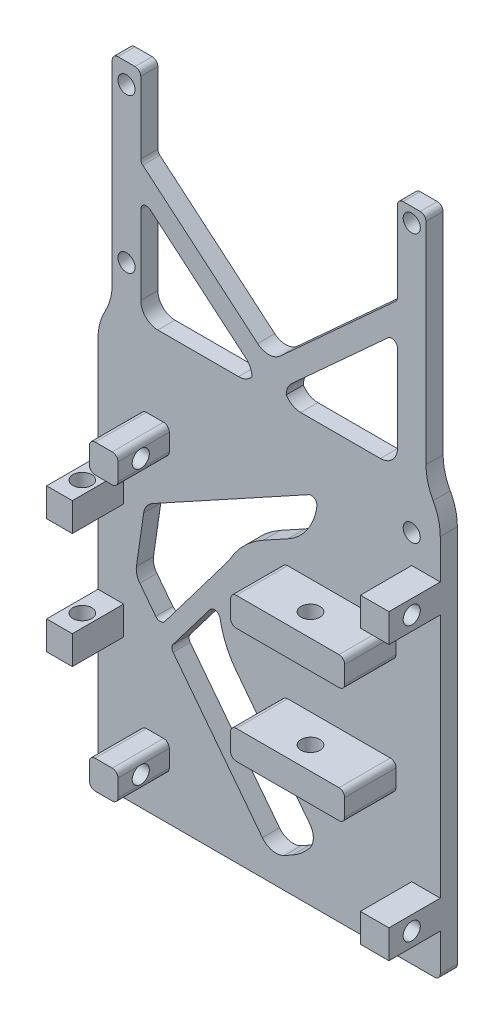
SolidWorks part; units mm, degrees
ref_plane "Front Plane" through (0, 0, 0) normal (0, 0, 1) x (1, 0, 0)
ref_plane "Top Plane" through (0, 0, 0) normal (0, 1, 0) x (1, 0, 0)
ref_plane "Right Plane" through (0, 0, 0) normal (1, 0, 0) x (0, 0, -1)
sketch "Sketch1" plane through (0, 0, 0) normal (0, 0, 1) x (1, 0, 0)
  line L1 (-63.7571, 35.9548) -> (-3.7571, 35.9548)
  line L2 (-63.7571, 35.9548) -> (-63.7571, -38.0452)
  line L3 (-63.7571, -38.0452) -> (-3.7571, -38.0452)
  line L4 (-3.7571, 35.9548) -> (-3.7571, -38.0452)
  dimension "D1" = 74
  dimension "D2" = 60
extrude "Boss-Extrude1" add sketch "Sketch1" along normal blind 3
sketch "Sketch2" plane through (0, 0, 3) normal (0, 0, 1) x (1, 0, 0)
  line L0 (-59.2571, -1.0452) -> (-63.7571, -1.0452) construction
  line L1 (-63.7571, 6.5548) -> (-59.2571, 6.5548) construction
  line L2 (-63.7571, 6.5548) -> (-63.7571, -8.6452) construction
  line L3 (-63.7571, -8.6452) -> (-59.2571, -8.6452) construction
  line L4 (-59.2571, 6.5548) -> (-59.2571, -8.6452) construction
  line L5 (-63.7571, 35.9548) -> (-63.7571, -38.0452) construction
  line L6 (-63.7571, -1.0452) -> (-3.7571, -1.0452) construction
  line L7 (-63.7571, 6.5548) -> (-59.2571, 6.5548)
  line L8 (-63.7571, 6.5548) -> (-63.7571, 11.5548)
  line L9 (-63.7571, 11.5548) -> (-59.2571, 11.5548)
  line L10 (-59.2571, 6.5548) -> (-59.2571, 11.5548)
  line L11 (-63.7571, -8.6452) -> (-59.2571, -8.6452)
  line L12 (-63.7571, -8.6452) -> (-63.7571, -13.6452)
  line L13 (-63.7571, -13.6452) -> (-59.2571, -13.6452)
  line L14 (-59.2571, -8.6452) -> (-59.2571, -13.6452)
  line L15 (-31.5071, -8.6452) -> (-11.5071, -8.6452)
  line L16 (-31.5071, -8.6452) -> (-31.5071, -13.6452)
  line L17 (-31.5071, -13.6452) -> (-11.5071, -13.6452)
  line L18 (-11.5071, -8.6452) -> (-11.5071, -13.6452)
  line L19 (-31.5071, -8.6452) -> (-11.5071, -13.6452) construction
  line L20 (-31.5071, -13.6452) -> (-11.5071, -8.6452) construction
  line L21 (-31.5071, 11.5548) -> (-11.5071, 11.5548)
  line L22 (-31.5071, 11.5548) -> (-31.5071, 6.5548)
  line L23 (-31.5071, 6.5548) -> (-11.5071, 6.5548)
  line L24 (-11.5071, 11.5548) -> (-11.5071, 6.5548)
  line L25 (-31.5071, 11.5548) -> (-11.5071, 6.5548) construction
  line L26 (-31.5071, 6.5548) -> (-11.5071, 11.5548) construction
  line L29 (-63.7571, -38.0452) -> (-3.7571, -38.0452) construction
  line L30 (-3.7571, -38.0452) -> (-3.7571, 35.9548) construction
  line L31 (-56.2571, -25.5452) -> (-51.2571, -25.5452)
  line L32 (-56.2571, -25.5452) -> (-56.2571, -30.5452)
  line L33 (-56.2571, -30.5452) -> (-51.2571, -30.5452)
  line L34 (-51.2571, -25.5452) -> (-51.2571, -30.5452)
  line L35 (-56.2571, -25.5452) -> (-51.2571, -30.5452) construction
  line L36 (-56.2571, -30.5452) -> (-51.2571, -25.5452) construction
  line L37 (-56.2571, 22.4548) -> (-51.2571, 22.4548)
  line L38 (-56.2571, 22.4548) -> (-56.2571, 17.4548)
  line L39 (-56.2571, 17.4548) -> (-51.2571, 17.4548)
  line L40 (-51.2571, 22.4548) -> (-51.2571, 17.4548)
  line L41 (-56.2571, 22.4548) -> (-51.2571, 17.4548) construction
  line L42 (-56.2571, 17.4548) -> (-51.2571, 22.4548) construction
  line L43 (-3.7571, -25.5452) -> (-8.7571, -25.5452)
  line L44 (-3.7571, -25.5452) -> (-3.7571, -30.5452)
  line L45 (-3.7571, -30.5452) -> (-8.7571, -30.5452)
  line L46 (-8.7571, -25.5452) -> (-8.7571, -30.5452)
  line L48 (-3.7571, 22.4548) -> (-8.7571, 22.4548)
  line L49 (-3.7571, 22.4548) -> (-3.7571, 17.4548)
  line L50 (-3.7571, 17.4548) -> (-8.7571, 17.4548)
  line L51 (-8.7571, 22.4548) -> (-8.7571, 17.4548)
  circle A0 centre (-61.5071, 9.0548) radius 1.5 construction
  circle A1 centre (-61.5071, -11.1452) radius 1.5 construction
  circle A2 centre (-21.5071, -11.1452) radius 1.3356 construction
  circle A3 centre (-21.5071, 9.0548) radius 1.3456 construction
  circle A4 centre (-53.7571, -28.0452) radius 1.5 construction
  circle A5 centre (-53.7571, 19.9548) radius 1.3233 construction
  point P8 (-63.7571, -1.0452)
  dimension "D7" = 3
  dimension "D8" = 3
  dimension "D9" = 40
  dimension "D10" = 40
  dimension "D12" = 2.25
  dimension "D13" = 2.5
  dimension "D14" = 2.5
  dimension "D15" = 2.25
  dimension "D19" = 10
  dimension "D20" = 10
  dimension "D21" = 3
  dimension "D24" = 48
  dimension "D1" = 15.2
  dimension "D2" = 4.5
  dimension "D3" = 0
  dimension "D4" = 0
  dimension "D5" = 5
  dimension "D6" = 5
  dimension "D11" = 7.6
  dimension "D16" = 20
  dimension "D17" = 20
  dimension "D18" = 7.6
  dimension "D22" = 5
  dimension "D23" = 5
  dimension "D25" = 5
  dimension "D26" = 5
  dimension "D27" = 5
  dimension "D28" = 5
extrude "Boss-Extrude2" add sketch "Sketch2" along normal blind 9
sketch "Sketch3" plane through (0, -13.6452, 0) normal (0, -1, 0) x (1, 0, 0)
  line L0 (-31.5071, 3) -> (-11.5071, 3) construction
  line L1 (-63.7571, 3) -> (-59.2571, 3) construction
  circle A0 centre (-21.5071, 8) radius 1.6536
  circle A1 centre (-61.5071, 8) radius 1.6536
  point P4 (-21.5071, 3)
  point P7 (-61.5071, 3)
  dimension "D1" = 5
  dimension "D2" = 5
extrude "Cut-Extrude1" cut sketch "Sketch3" against normal blind 26
sketch "Sketch4" plane through (-56.2571, 0, 0) normal (-1, 0, 0) x (0, 0, 1)
  line L0 (3, -25.5452) -> (3, -30.5452) construction
  line L1 (3, 22.4548) -> (3, 17.4548) construction
  circle A0 centre (8, 19.9548) radius 1.5
  circle A1 centre (8, -28.0452) radius 1.5
  dimension "D1" = 3
  dimension "D2" = 3
  dimension "D3" = 5
  dimension "D4" = 5
extrude "Cut-Extrude2" cut sketch "Sketch4" against normal blind 59
sketch "Sketch5" plane through (0, 0, 3) normal (0, 0, 1) x (1, 0, 0)
  line L0 (-58.7571, 27.4548) -> (-8.7571, 27.4548) construction
  line L1 (-63.7571, 35.9548) -> (-63.7571, 11.5548) construction
  line L2 (-3.7571, 22.4548) -> (-8.7571, 22.4548) construction
  line L3 (-3.7571, 35.9548) -> (-63.7571, 35.9548) construction
  line L4 (-3.7571, 22.4548) -> (-3.7571, 35.9548) construction
  line L6 (-61.2571, 35.9548) -> (-56.2571, 35.9548)
  line L7 (-61.2571, 35.9548) -> (-61.2571, 73.9548)
  line L8 (-61.2571, 73.9548) -> (-56.2571, 73.9548)
  line L9 (-56.2571, 35.9548) -> (-56.2571, 73.9548)
  line L10 (-6.2571, 35.9548) -> (-11.2571, 35.9548)
  line L11 (-6.2571, 35.9548) -> (-6.2571, 76.9548)
  line L12 (-6.2571, 76.9548) -> (-11.2571, 76.9548)
  line L13 (-11.2571, 35.9548) -> (-11.2571, 76.9548)
  circle A0 centre (-58.7571, 27.4548) radius 1.3883 construction
  circle A1 centre (-8.7571, 27.4548) radius 1.4141
  circle A2 centre (-8.7571, 74.4548) radius 1.5
  circle A3 centre (-58.7571, 70.4548) radius 1.5
  circle A4 centre (-58.7571, 43.4548) radius 1.5
  dimension "D2" = 5
  dimension "D3" = 5
  dimension "D4" = 47
  dimension "D5" = 3
  dimension "D6" = 4
  dimension "D7" = 3
  dimension "D8" = 27
  dimension "D9" = 3
  dimension "D10" = 38.5
  dimension "D11" = 5
  dimension "D12" = 34.5
  dimension "D1" = 50
  dimension "D13" = 38
  dimension "D14" = 5
  dimension "D15" = 5
  dimension "D16" = 2.5
  dimension "D17" = 2.5
  dimension "D18" = 41
extrude "Boss-Extrude3" add sketch "Sketch5" against normal blind 3
sketch "Sketch6" plane through (0, 0, 3) normal (0, 0, 1) x (1, 0, 0)
  circle A0 centre (-8.7571, 27.4548) radius 1.5
  circle A1 centre (-8.7571, 74.4548) radius 1.5 construction
  dimension "D1" = 3
  dimension "D2" = 47
extrude "Cut-Extrude3" cut sketch "Sketch6" against normal blind 3
sketch "Sketch7" plane through (0, 0, 3) normal (0, 0, 1) x (1, 0, 0)
  line L0 (-56.2571, 54.9548) -> (-36.7571, 38.4881)
  line L1 (-56.2571, 35.9548) -> (-56.2571, 73.9548) construction
  line L2 (-11.2571, 35.9548) -> (-56.2571, 35.9548) construction
  line L3 (-30.7571, 38.6881) -> (-30.7571, 35.9548)
  line L4 (-33.7571, 40.9548) -> (-56.2571, 59.9548)
  line L5 (-56.2571, 59.9548) -> (-56.2571, 54.9548)
  line L6 (-30.7571, 38.6881) -> (-11.2571, 56.4548)
  line L7 (-11.2571, 76.9548) -> (-11.2571, 35.9548) construction
  line L8 (-33.7571, 40.9548) -> (-11.2571, 61.4548)
  line L9 (-11.2571, 61.4548) -> (-11.2571, 56.4548)
  line L10 (-36.7571, 38.4881) -> (-36.7571, 35.9548)
  line L11 (-36.7571, 35.9548) -> (-30.7571, 35.9548)
  dimension "D2" = 5
  dimension "D3" = 5
extrude "Boss-Extrude4" add sketch "Sketch7" against normal blind 3
fillet "Fillet1" radius 10 1 edges at (-3.7571, 35.9548, 1.5)
fillet "Fillet2" radius 10 1 edges at (-63.7571, 35.9548, 1.5)
fillet "Fillet3" radius 10 1 edges at (-6.2571, 35.9548, 1.5)
fillet "Fillet4" radius 10 1 edges
fillet "Fillet5" radius 3 1 edges at (-33.7571, 40.9548, 1.5)
fillet "Fillet6" radius 3 1 edges at (-30.7571, 38.6881, 1.5)
fillet "Fillet7" radius 3 1 edges at (-30.7571, 35.9548, 1.5)
fillet "Fillet8" radius 3 1 edges at (-36.7571, 38.4881, 1.5)
fillet "Fillet9" radius 3 1 edges at (-36.7571, 35.9548, 1.5)
fillet "Fillet10" radius 3 1 edges at (-11.2571, 35.9548, 1.5)
fillet "Fillet11" radius 3 1 edges
fillet "Fillet12" radius 1 1 edges at (-56.2571, 54.9548, 1.5)
fillet "Fillet13" radius 1 1 edges at (-11.2571, 56.4548, 1.5)
fillet "Fillet14" radius 1 1 edges at (-11.2571, 61.4548, 1.5)
fillet "Fillet15" radius 1 1 edges at (-56.2571, 59.9548, 1.5)
sketch "Sketch8" plane through (0, 0, 3) normal (0, 0, 1) x (1, 0, 0)
  line L0 (-50.1166, 4.8667) -> (-25.396, -27.3062)
  line L1 (-55.535, 8.4095) -> (-57.2022, -3.0525)
  line L2 (-33.3696, -33.9846) -> (-57.2022, -3.0525)
  line L4 (-25.396, -27.3062) -> (-13.8548, -23.2674)
  line L5 (-13.8548, -23.2674) -> (-33.3696, -33.9846)
  line L6 (-55.535, 8.4095) -> (-25.3161, 25.0052)
  line L7 (-25.3161, 25.0052) -> (-22.5658, 19.9971)
  line L8 (-22.5658, 19.9971) -> (-47.1909, 6.4734)
  line L9 (-47.1909, 6.4734) -> (-50.1166, 4.8667)
extrude "Cut-Extrude4" cut sketch "Sketch8" against normal blind 3
fillet "Fillet16" radius 15 1 edges at (-50.1166, 4.8667, 1.5)
fillet "Fillet17" radius 10 1 edges at (-22.5658, 19.9971, 1.5)
fillet "Fillet18" radius 10 1 edges at (-13.8548, -23.2674, 1.5)
fillet "Fillet19" radius 3 1 edges at (-33.3696, -33.9846, 1.5)
fillet "Fillet20" radius 3 1 edges at (-25.396, -27.3062, 1.5)
fillet "Fillet21" radius 3 1 edges at (-55.535, 8.4095, 1.5)
fillet "Fillet22" radius 3 1 edges at (-57.2022, -3.0525, 1.5)
fillet "Fillet23" radius 1 1 edges at (-25.3161, 25.0052, 1.5)
fillet "Fillet24" radius 1 1 edges at (-3.7571, -38.0452, 1.5)
fillet "Fillet25" radius 1 1 edges at (-63.7571, -38.0452, 1.5)
fillet "Fillet26" radius 1 1 edges at (-6.2571, 76.9548, 1.5)
fillet "Fillet27" radius 1 1 edges at (-11.2571, 76.9548, 1.5)
fillet "Fillet28" radius 1 1 edges at (-56.2571, 73.9548, 1.5)
fillet "Fillet29" radius 1 1 edges at (-61.2571, 73.9548, 1.5)
sketch "Sketch9" plane through (0, 0, 3) normal (0, 0, 1) x (1, 0, 0)
  line L0 (-52.8267, -8.7315) -> (-40.8167, 7.1683)
  line L1 (-56.4271, -4.0586) -> (-34.9379, -31.9492) construction
  line L2 (-51.0528, -11.0339) -> (-42.5664, 0.1377)
  line L3 (-52.8267, -8.7315) -> (-51.0528, -11.0339)
  arc A0 (-34.7869, 13.2855) -> (-39.4607, -9.0015) centre (-27.5664, 0.1377) ccw construction
  arc A1 (-40.8167, 7.1683) -> (-42.5664, 0.1377) centre (-27.5664, 0.1377) ccw
extrude "Boss-Extrude5" add sketch "Sketch9" against normal blind 3
fillet "Fillet30" radius 1 1 edges at (-51.0528, -11.0339, 1.5)
fillet "Fillet31" radius 1 1 edges at (-52.8267, -8.7315, 1.5)
fillet "Fillet32" radius 1 1 edges at (-42.5664, 0.1377, 1.5)
fillet "Fillet33" radius 1 1 edges at (-11.5071, 6.5548, 7.5)
fillet "Fillet34" radius 1 1 edges at (-11.5071, 11.5548, 7.5)
fillet "Fillet35" radius 1 1 edges at (-31.5071, 6.5548, 7.5)
fillet "Fillet36" radius 1 1 edges at (-31.5071, 11.5548, 7.5)
fillet "Fillet37" radius 1 1 edges at (-11.5071, -13.6452, 7.5)
fillet "Fillet38" radius 1 1 edges at (-11.5071, -8.6452, 7.5)
fillet "Fillet39" radius 1 1 edges at (-31.5071, -13.6452, 7.5)
fillet "Fillet40" radius 1 1 edges at (-31.5071, -8.6452, 7.5)
fillet "Fillet41" radius 1 1 edges at (-51.2571, -30.5452, 7.5)
fillet "Fillet42" radius 1 1 edges at (-56.2571, -30.5452, 7.5)
fillet "Fillet43" radius 1 6 edges at (-56.2571, 22.4548, 7.5) (-51.2571, 22.4548, 7.5) (-56.2571, 17.4548, 7.5) (-51.2571, 17.4548, 7.5) (-56.2571, -25.5452, 7.5) (-51.2571, -25.5452, 7.5)
